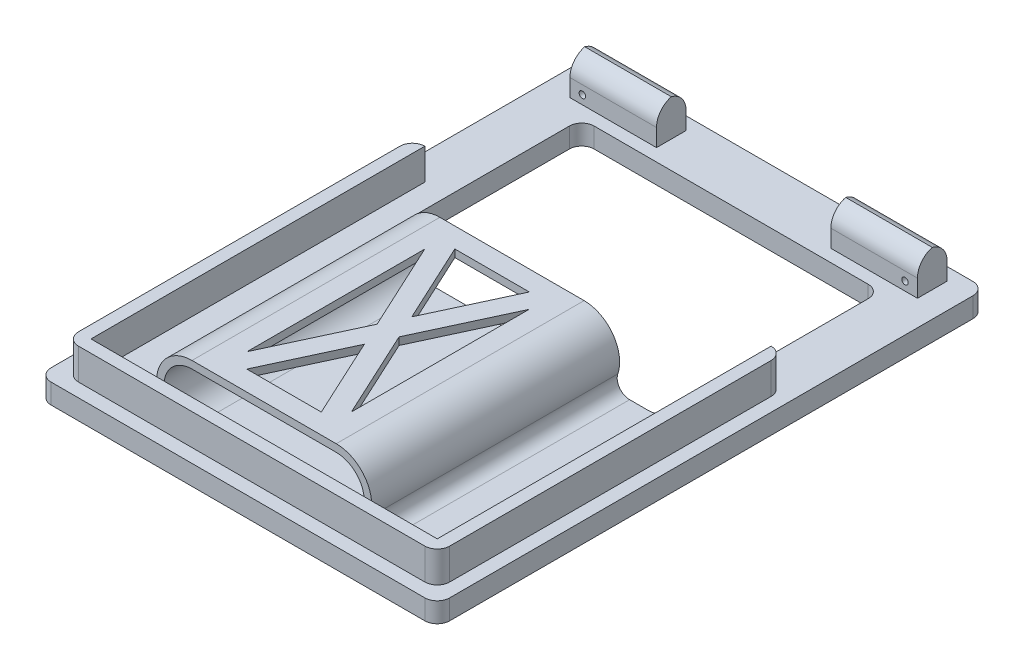
SolidWorks part; units mm, degrees
ref_plane "Front Plane" through (0, 0, 0) normal (0, 0, 1) x (1, 0, 0)
ref_plane "Top Plane" through (0, 0, 0) normal (0, 1, 0) x (1, 0, 0)
ref_plane "Right Plane" through (0, 0, 0) normal (1, 0, 0) x (0, 0, -1)
sketch "Sketch3" plane through (0, 0, 0) normal (0, 1, 0) x (1, 0, 0)
  line L0 (-75, 110) -> (75, 110)
  line L1 (-75, -105) -> (75, -105)
  line L2 (-75, -105) -> (-75, 105)
  line L4 (75, -105) -> (75, 105)
  line L5 (-75, -105) -> (75, 105) construction
  line L6 (-75, 105) -> (75, -105) construction
  line L7 (80, -105) -> (80, 105)
  line L8 (-75, -110) -> (75, -110)
  line L9 (-80, -105) -> (-80, 105)
  line L10 (-80, -110) -> (80, -110) construction
  line L11 (-80, -110) -> (-80, 110) construction
  line L12 (80, -110) -> (80, 110) construction
  line L13 (-80, 110) -> (80, 110) construction
  line L15 (-75, 105) -> (75, 105)
  line L19 (-75, 105) -> (75, 105) construction
  line L20 (-69.75, 104.9) -> (69.75, 104.9)
  line L21 (-69.75, 104.9) -> (-69.75, 93)
  line L22 (-69.75, 93) -> (69.75, 93)
  line L23 (69.75, 104.9) -> (69.75, 93)
  arc A0 (-75, -110) -> (-80, -105) centre (-75, -105) cw
  arc A1 (80, -105) -> (75, -110) centre (75, -105) cw
  arc A2 (75, 110) -> (80, 105) centre (75, 105) cw
  arc A3 (-75, 110) -> (-80, 105) centre (-75, 105) ccw
  point P0 (0, 0)
  point P5 (0, 93)
  dimension "D4" = 5
  dimension "D1" = 75
  dimension "D2" = 210
  dimension "D5" = 11.9
  dimension "D6" = 139.5
  dimension "D7" = 0.1
  dimension "D3" = 5
extrude "Boss-Extrude1" add sketch "Sketch3" along normal blind 8 contours L1 L4 L2 | L0 A3 L9 A0 L8 A1 L7 A2 L4 L1 L2 | L2 L4 | L23 L15 L21 L22 region at (0, 0, -107.2797) region at (0, 0, 5.5048) region at (0, 0, -98.95)
extrude "Boss-Extrude2" add sketch "Sketch3<7>" along normal blind 15 from surface contours L23 L15 L21 L22 region at (0, 0, -98.95) starting at face at (0, 8, 0)
sketch "Sketch3<7>" plane through (0, 0, 0) normal (0, 1, 0) x (1, 0, 0) same geometry as "Sketch3"
fillet "Fillet1" radius 8 2 edges at (0, 23, -93) (0, 23, -104.9)
sketch "Sketch4" plane through (0, 0, 0) normal (0, -1, 0) x (1, 0, 0)
  line L0 (69.75, -93) -> (-69.75, -93) construction
  line L1 (-55, 0) -> (55, 0)
  line L2 (-60, -5) -> (-60, -83)
  line L3 (-55, -88) -> (55, -88)
  line L4 (60, -5) -> (60, -83)
  line L5 (-75, 110) -> (75, 110) construction
  line L6 (80, 105) -> (80, -105) construction
  arc A0 (-55, 0) -> (-60, -5) centre (-55, -5) ccw
  arc A1 (-60, -83) -> (-55, -88) centre (-55, -83) ccw
  arc A2 (55, -88) -> (60, -83) centre (55, -83) ccw
  arc A3 (55, 0) -> (60, -5) centre (55, -5) cw
  point P4 (0, -88)
  dimension "D4" = 5
  dimension "D1" = 5
  dimension "D2" = 110
  dimension "D3" = 20
extrude "Cut-Extrude1" cut sketch "Sketch4" against normal up to next
sketch "Sketch5" plane through (0, 8, 0) normal (0, 1, 0) x (1, 0, 0)
  line L0 (75, -105) -> (75, 105) construction
  line L1 (-75, -105) -> (75, -105) construction
  line L2 (-75, -105) -> (-75, 105) construction
  line L3 (-75, 105) -> (75, 105) construction
  line L4 (75, 110) -> (-75, 110)
  line L5 (80, -105) -> (80, 105)
  line L6 (-75, -110) -> (75, -110)
  line L7 (-80, 105) -> (-80, -105)
  line L8 (75, 110) -> (-75, 110)
  line L9 (80, -105) -> (80, 105)
  line L10 (-75, -110) -> (75, -110)
  line L11 (-80, 105) -> (-80, -105)
  line L12 (69.75, 104.9) -> (-69.75, 104.9)
  line L13 (-69.75, 104.9) -> (-69.75, 93)
  line L14 (-69.75, 93) -> (69.75, 93)
  line L15 (69.75, 93) -> (69.75, 104.9)
  line L16 (69.75, 104.9) -> (-69.75, 104.9)
  line L17 (-69.75, 104.9) -> (-69.75, 93)
  line L18 (-69.75, 93) -> (69.75, 93)
  line L19 (69.75, 93) -> (69.75, 104.9)
  line L20 (75, -105) -> (75, 105)
  line L21 (-75, -105) -> (75, -105)
  line L22 (-75, -105) -> (-75, 105)
  line L23 (-75, 105) -> (75, 105)
  line L24 (-75, 35) -> (75, 35)
  line L25 (-69.5, 34.5) -> (-69.5, -99.5)
  line L26 (-69.5, -104.5) -> (69.5, -104.5)
  line L27 (-74.5, -99.5) -> (-74.5, 29.5)
  line L28 (-69.5, 34.5) -> (69.5, 34.5)
  line L29 (74.5, -99.5) -> (74.5, 29.5)
  line L30 (-69.5, -99.5) -> (69.5, -99.5)
  line L31 (69.5, -99.5) -> (69.5, 34.5)
  arc A0 (-74.5, 29.5) -> (-69.5, 34.5) centre (-69.5, 29.5) cw
  arc A1 (69.5, 34.5) -> (74.5, 29.5) centre (69.5, 29.5) cw
  arc A2 (69.5, -104.5) -> (74.5, -99.5) centre (69.5, -99.5) ccw
  arc A3 (-69.5, -104.5) -> (-74.5, -99.5) centre (-69.5, -99.5) cw
  arc A4 (80, 105) -> (75, 110) centre (75, 105) ccw
  arc A5 (75, -110) -> (80, -105) centre (75, -105) ccw
  arc A6 (-80, -105) -> (-75, -110) centre (-75, -105) ccw
  arc A7 (-75, 110) -> (-80, 105) centre (-75, 105) ccw
  arc A8 (80, 105) -> (75, 110) centre (75, 105) ccw
  arc A9 (75, -110) -> (80, -105) centre (75, -105) ccw
  arc A10 (-80, -105) -> (-75, -110) centre (-75, -105) ccw
  arc A11 (-75, 110) -> (-80, 105) centre (-75, 105) ccw
  point P26 (0, -104.5)
  point P42 (0, -99.5)
  dimension "D7" = 5
  dimension "D3" = 75
  dimension "D4" = 0.5
  dimension "D5" = 0.5
  dimension "D6" = 0.5
  dimension "D8" = 5
  dimension "D9" = 5
  dimension "D1" = 0
  dimension "D2" = 0
extrude "Boss-Extrude3" add sketch "Sketch5" along normal blind 12.5 contours A3 L26 A2 L29 A1 L31 L30 L25 A0 L27 region at (-71.5377, 8, 32.5)
sketch "Sketch6" plane through (0, 0, -104.9) normal (0, 0, -1) x (-1, 0, 0)
  line L0 (-69.75, 15) -> (-69.75, 8) construction
  line L1 (0, 0) -> (0, 22.7329) construction
  line L2 (-69.75, 22.7329) -> (69.75, 22.7329) construction
  circle A0 centre (-64.75, 11.5) radius 1.3
  circle A1 centre (64.75, 11.5) radius 1.3
  point P5 (-69.75, 11.5)
  dimension "D1" = 2.6
  dimension "D2" = 5
extrude "Cut-Extrude2" cut sketch "Sketch6" against normal up to next
sketch "Sketch8" plane through (0, 0, 99.5) normal (0, 0, -1) x (-1, 0, 0)
  line L0 (-28.95, 19.05) -> (28.95, 19.05) construction
  line L1 (-28.95, 30.1) -> (28.95, 30.1)
  line L2 (-28.95, 8) -> (28.95, 8)
  line L3 (69.5, 8) -> (-69.5, 8) construction
  line L4 (0, 19.05) -> (0, 0) construction
  line L5 (-28.95, 30.3) -> (28.95, 30.3)
  line L6 (-28.95, 7.8) -> (28.95, 7.8)
  line L7 (-28.95, 33.3) -> (28.95, 33.3)
  line L8 (-28.95, 4.8) -> (28.95, 4.8)
  line L9 (-37.9478, 8) -> (37.9478, 8)
  arc A0 (-28.95, 30.1) -> (-28.95, 8) centre (-28.95, 19.05) ccw
  arc A1 (28.95, 8) -> (28.95, 30.1) centre (28.95, 19.05) ccw
  arc A2 (28.95, 7.8) -> (28.95, 30.3) centre (28.95, 19.05) ccw
  arc A3 (-28.95, 30.3) -> (-28.95, 7.8) centre (-28.95, 19.05) ccw
  arc A4 (28.95, 4.8) -> (28.95, 33.3) centre (28.95, 19.05) ccw
  arc A5 (-28.95, 33.3) -> (-28.95, 4.8) centre (-28.95, 19.05) ccw
  point P2 (0, 19.05)
  line M6 (-69.5, 8) -> (69.5, 8)
  line M8 (69.5, 20.5) -> (-69.5, 20.5)
  dimension "D2" = 80
  dimension "D1" = 22.1
  dimension "D3" = 0.2
  dimension "D4" = 3
extrude "Boss-Extrude4" add sketch "Sketch8" along normal up to surface (99.5 mm away) contours L7 A5 A3 L5 A2 A4 M8 | L9 A4 A2 M8 | A5 A3 M8 M6 region at (41.6161, 21.372, 99.5) region at (39.5627, 13.5654, 99.5) region at (-39.5627, 13.5654, 99.5) up to face at (0, 4, 0)
fillet "Fillet2" radius 5 2 edges at (-37.9478, 8, 49.75) (37.9478, 8, 49.75)
sketch "Sketch9" plane through (0, 8, 0) normal (0, 1, 0) x (1, 0, 0)
  line L0 (69.75, 98.95) -> (-69.75, 98.95) construction
  line L1 (-35, 104.9) -> (35, 104.9)
  line L2 (-35, 104.9) -> (-35, 93)
  line L3 (-35, 93) -> (35, 93)
  line L4 (35, 104.9) -> (35, 93)
  line L5 (-35, 104.9) -> (35, 93) construction
  line L6 (-35, 93) -> (35, 104.9) construction
  line L7 (69.75, 93) -> (-69.75, 93) construction
  point P0 (0, 98.95)
  dimension "D1" = 70
extrude "Cut-Extrude3" cut sketch "Sketch9" along normal up to next
sketch "Sketch10" plane through (0, 33.3, 0) normal (0, 1, 0) x (1, 0, 0)
  line L0 (-20.95, -85.4223) -> (-4.4091, -49.75)
  line L1 (-4.4091, -49.75) -> (-20.95, -14.0777)
  line L2 (-14.95, -8) -> (0, -40.2413)
  line L3 (0, -40.2413) -> (14.95, -8)
  line L4 (28.95, 0) -> (-28.95, 0)
  line L5 (-28.95, 0) -> (-28.95, -99.5)
  line L6 (-28.95, -99.5) -> (28.95, -99.5)
  line L7 (28.95, -99.5) -> (28.95, 0)
  line L8 (28.95, 0) -> (-28.95, 0)
  line L9 (-28.95, 0) -> (-28.95, -99.5)
  line L10 (-28.95, -99.5) -> (28.95, -99.5)
  line L11 (28.95, -99.5) -> (28.95, 0)
  line L12 (0, -8) -> (0, -91.5) construction
  line L13 (20.95, -49.75) -> (-20.95, -49.75) construction
  line L14 (20.95, -85.4223) -> (4.4091, -49.75)
  line L15 (4.4091, -49.75) -> (20.95, -14.0777)
  line L16 (20.95, -8) -> (-20.95, -8)
  line L17 (-20.95, -8) -> (-20.95, -91.5)
  line L18 (-20.95, -91.5) -> (20.95, -91.5)
  line L19 (20.95, -91.5) -> (20.95, -8)
  line L20 (20.95, -8) -> (-20.95, -8)
  line L21 (-20.95, -8) -> (-20.95, -91.5)
  line L22 (-20.95, -91.5) -> (20.95, -91.5)
  line L23 (20.95, -91.5) -> (20.95, -8)
  line L24 (0, -59.2587) -> (14.95, -91.5)
  line L25 (-14.95, -91.5) -> (0, -59.2587)
  point P18 (-5.724, -49.75)
  point P19 (-16.046, -8)
  point P20 (-20.95, -19.3893)
  point P21 (-20.95, -84.5499)
  dimension "D3" = 8
  dimension "D4" = 6
  dimension "D1" = 0
  dimension "D2" = 8
extrude "Cut-Extrude4" cut sketch "Sketch10" against normal up to next contours L14 L23 L15 | L25 L22 L24 | L3 L20 L2 | L1 L21 L0 region at (-15.4364, 33.3, 49.75) region at (0, 33.3, 80.7529) region at (0, 33.3, 18.7471) region at (15.4364, 33.3, 49.75)
